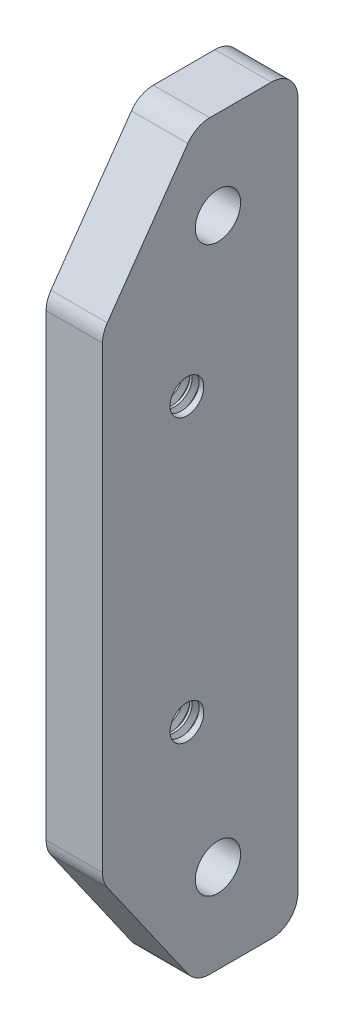
SolidWorks part; units mm, degrees
ref_plane "Front Plane" through (0, 0, 0) normal (0, 0, 1) x (1, 0, 0)
ref_plane "Top Plane" through (0, 0, 0) normal (0, 1, 0) x (1, 0, 0)
ref_plane "Right Plane" through (0, 0, 0) normal (1, 0, 0) x (0, 0, -1)
sketch "Sketch1" plane through (0, 0, 0) normal (1, 0, 0) x (0, 0, -1)
  line L0 (0, 0) -> (9, 0) construction
  line L1 (0, -31.75) -> (0, 31.75) construction
  line L2 (-12.4312, 25.4) -> (9, 25.4) construction
  line L3 (-12.4312, 25.4) -> (-12.4312, -25.4) construction
  line L4 (-12.4312, -25.4) -> (9, -25.4) construction
  line L5 (9, 25.4) -> (9, -25.4) construction
  line L6 (-3.4937, -15.875) -> (-3.4937, 15.875) construction
  line L8 (-12.9937, 41.75) -> (9, 41.75)
  line L9 (-12.9937, 41.75) -> (-12.9937, -41.75)
  line L10 (-12.9937, -41.75) -> (9, -41.75)
  line L11 (9, 41.75) -> (9, -41.75)
  circle A0 centre (0, 31.75) radius 2.55
  circle A1 centre (0, -31.75) radius 2.55
  circle A2 centre (-3.4937, 15.875) radius 1.8986
  circle A3 centre (-3.4937, -15.875) radius 1.8986
  point P6 (0, 0)
  point P16 (-3.4937, 0)
  dimension "D1" = 5.1
  dimension "D2" = 5.1
  dimension "D12" = 3.7973
  dimension "D13" = 3.7973
  dimension "D3" = 63.5
  dimension "D4" = 50.8
  dimension "D5" = 21.4312
  dimension "D6" = 31.75
  dimension "D7" = 12.4938
  dimension "D8" = 9
  dimension "D9" = 10
  dimension "D10" = 10
  dimension "D11" = 9.5
extrude "Boss-Extrude1" add sketch "Sketch1" along normal blind 3.175 and the other way blind 3.175
chamfer "Chamfer1" distance 15 angle 35 1 edges at (0, 41.75, 12.9937) first distance on face at (0, 0, 12.9937)
chamfer "Chamfer2" distance 15 angle 35 1 edges at (0, -41.75, 12.9937) first distance on face at (0, -7.5, 12.9937)
thread "Thread1" pitch 1.0583 method cut profile "Thread Profile1" start angle 0, offset 0, length 10, pitch 1.0583, diameter 3.7973
ref_plane "Plane1" through (3.175, 15.875, 5.3924) normal (0, -1, 0) x (0, 0, 1)
sketch "Thread Profile1" plane through (3.175, 15.875, 5.3924) normal (0, -1, 0) x (0, 0, 1)
  line L0 (0, 0) -> (0, 1.0583) construction
  line L1 (0, 0) -> (0.5728, 0.3307)
  line L2 (0.5728, 0.3307) -> (0.5728, 0.463)
  line L3 (0.5728, 0.463) -> (0, 0.7937)
  line L4 (0.5728, 0.3969) -> (0, 0.3969) construction
  line L11 (0, 0) -> (0, 0.7937)
  point P2 (0, 0)
  dimension "Pitch" = 1.0583
  dimension "Profile_Angle" = 60
  dimension "Profile_Land" = 0.1323
  dimension "Profile_Height" = 0.5728
thread "Thread2" pitch 1.0583 method cut profile "Thread Profile2" start angle 0, offset 0, length 10, pitch 1.0583, diameter 3.7973
ref_plane "Plane2" through (3.175, -15.875, 5.3924) normal (0, -1, 0) x (0, 0, 1)
sketch "Thread Profile2" plane through (3.175, -15.875, 5.3924) normal (0, -1, 0) x (0, 0, 1)
  line L0 (0, 0) -> (0, 1.0583) construction
  line L1 (0, 0) -> (0.5728, 0.3307)
  line L2 (0.5728, 0.3307) -> (0.5728, 0.463)
  line L3 (0.5728, 0.463) -> (0, 0.7937)
  line L4 (0.5728, 0.3969) -> (0, 0.3969) construction
  line L11 (0, 0) -> (0, 0.7937)
  point P2 (0, 0)
  dimension "Pitch" = 1.0583
  dimension "Profile_Angle" = 60
  dimension "Profile_Land" = 0.1323
  dimension "Profile_Height" = 0.5728
fillet "Fillet1" radius 3 6 edges at (0, -26.75, 12.9937) (0, -41.75, -9) (0, -41.75, 2.4906) (0, 41.75, -9) (0, 41.75, 2.4906) (0, 26.75, 12.9937)
